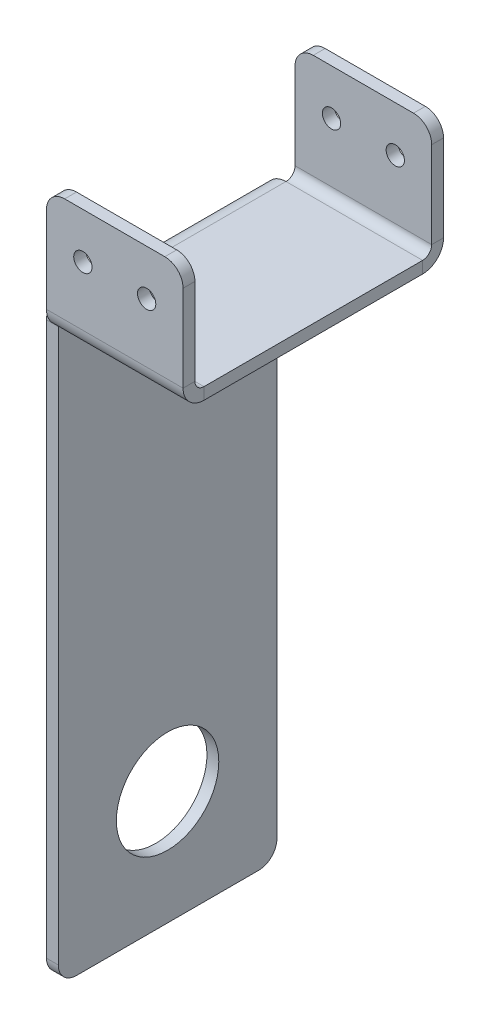
SolidWorks part; units mm, degrees
note: The reader was unsure of these and kept them because the rebuilt part matched: thickness of "Base-Flange1", "Edge-Flange1", "Edge-Flange2", "Sheet-Metal1", "Sheet-Metal2", "Sheet-Metal3", "Sheet-Metal4", "Sheet-Metal5", "Sheet-Metal6"; flange length of "Edge-Flange1", "Edge-Flange2".
ref_plane "Front Plane" through (0, 0, 0) normal (0, 0, 1) x (1, 0, 0)
ref_plane "Top Plane" through (0, 0, 0) normal (0, 1, 0) x (1, 0, 0)
ref_plane "Right Plane" through (0, 0, 0) normal (1, 0, 0) x (0, 0, -1)
sketch "Sketch1" plane through (0, 0, 0) normal (0, 1, 0) x (1, 0, 0)
  line L1 (-19.05, -30.48) -> (19.05, -30.48)
  line L2 (-19.05, -30.48) -> (-19.05, 30.48)
  line L3 (-19.05, 30.48) -> (19.05, 30.48)
  line L4 (19.05, -30.48) -> (19.05, 30.48)
  line L5 (-19.05, -30.48) -> (19.05, 30.48) construction
  line L6 (-19.05, 30.48) -> (19.05, -30.48) construction
  point P1 (0, 0)
  dimension "D1" = 38.1
  dimension "D2" = 60.96
base flange "Base-Flange1" sketch "Sketch1" thickness 3.302 reverse thickness direction no parameters "D1"=2.54
edge flange "Edge-Flange1" sketch "Sketch10" flange profiles "Sketch10", "Sketch11" flange angle 90 flange length 35.052 flange position bend outside bend radius 2.54 thickness 3.302 relief rectangular parameters "D6"=10, "D8"=0.254
sketch "Sketch10" plane through (0, 0, 30.48) normal (0, 0, 1) x (1, 0, 0)
  line L0 (-19.05, 0) -> (19.05, 0) construction
  line L1 (-19.05, 0) -> (19.05, 0)
  line L2 (-19.05, 0) -> (-19.05, 31.75)
  line L3 (-19.05, 31.75) -> (19.05, 31.75)
  line L4 (19.05, 31.75) -> (19.05, 0)
sketch "Sketch11" plane through (0, 0, -30.48) normal (0, 0, -1) x (-1, 0, 0)
  line L0 (-19.05, 0) -> (19.05, 0) construction
  line L1 (-19.05, 0) -> (19.05, 0)
  line L2 (-19.05, 0) -> (-19.05, 31.75)
  line L3 (-19.05, 31.75) -> (19.05, 31.75)
  line L4 (19.05, 31.75) -> (19.05, 0)
bend "EdgeBend1" bend radius 2.54 bend angle 90 parameters "D5"=1
bend "EdgeBend2" bend radius 2.54 bend angle 90 parameters "D5"=2
edge flange "Edge-Flange2" sketch "Sketch16" flange angle 90 flange length 165.1 flange position bend outside bend radius 2.54 thickness 3.302 parameters "D6"=10
sketch "Sketch16" plane through (-19.05, -3.302, 0) normal (-1, 0, 0) x (0, 0, -1)
  line L0 (30.48, 0) -> (-30.48, 0) construction
  line L1 (30.48, 0) -> (-30.48, 0)
  line L2 (-30.48, 0) -> (-30.48, 161.798)
  line L3 (-30.48, 161.798) -> (30.48, 161.798)
  line L4 (30.48, 161.798) -> (30.48, 0)
bend "EdgeBend3" bend radius 2.54 bend angle 90 parameters "D5"=3
sketch "Sketch17" plane through (-24.892, 0, 0) normal (-1, 0, 0) x (0, 0, 1)
  line L0 (-30.48, -165.1) -> (30.48, -165.1) construction
  circle A0 centre (0, -133.2738) radius 14.2812
  dimension "D1" = 28.5623
  dimension "D2" = 31.8262
extrude "Cut-Extrude1" cut sketch "Sketch17" against normal through all contours A0 normal cut yes
sketch "Sketch18" plane through (0, 0, 36.322) normal (0, 0, 1) x (1, 0, 0)
  line L0 (19.05, 31.75) -> (-19.05, 31.75) construction
  line L1 (19.05, 2.54) -> (19.05, 31.75) construction
  line L2 (-19.05, 31.75) -> (-19.05, 2.54) construction
  circle A0 centre (8.89, 19.05) radius 2.5527
  circle A1 centre (-8.89, 19.05) radius 2.5527
  dimension "D1" = 5.1054
  dimension "D2" = 5.1054
  dimension "D3" = 12.7
  dimension "D4" = 12.7
  dimension "D5" = 10.16
  dimension "D6" = 10.16
extrude "Cut-Extrude2" [suppressed] cut sketch "Sketch18" against normal through all
hole_wizard "1/4-20 Tapped Hole1" positions "Sketch19" profile "Sketch20" tap size "1/4-20" standard "ANSI Inch" end condition through all
sketch "Sketch19" plane through (0, 0, 36.322) normal (0, 0, 1) x (1, 0, 0)
  line L0 (19.05, 31.75) -> (-19.05, 31.75) construction
  line L1 (-19.05, 31.75) -> (-19.05, 2.54) construction
  line L2 (19.05, 2.54) -> (19.05, 31.75) construction
  point P0 (8.89, 19.05)
  point P2 (-8.89, 19.05)
  dimension "D1" = 12.7
  dimension "D2" = 12.7
  dimension "D3" = 10.16
  dimension "D4" = 10.16
sketch "Sketch20" plane through (8.89, 19.05, 36.322) normal (1, 0, 0) x (0, -1, 0)
  line L0 (0, 0) -> (0, 72.644)
  line L1 (0, 72.644) -> (2.5527, 72.644)
  line L2 (2.5527, 72.644) -> (2.5527, 0)
  line L5 (2.5527, 0) -> (0, 0)
  line L11 (0, -6.35) -> (0, 107.95) construction
  dimension "Thru Tap Drill Dia." = 5.1054
  dimension "Thru Tap Drill Depth" = 72.644
cosmetic thread "Hole Thread1"
cosmetic thread "Hole Thread2"
fillet "Fillet1" radius 5.08 6 edges at (-19.05, 31.75, 34.671) (19.05, 31.75, 34.671) (-19.05, 31.75, -34.671) (19.05, 31.75, -34.671) (-23.241, -165.1, -30.48) (-23.241, -165.1, 30.48)
sketch "Bend-Lines1" [suppressed] plane through (0, 0, 0) normal (0, 1, 0) x (1, 0, 0)
sketch "Bounding-Box1" [suppressed] plane through (0, 0, 0) normal (0, 1, 0) x (1, 0, 0)
sheet metal parameters "Sheet-Metal1" thickness 3.302 parameters "D1"=2.54, "D7"=1.6129
flat pattern "Flat-Pattern1" [suppressed]
sketch "Bend-Lines2" plane through (0, 0, 0) normal (0, 1, 0) x (1, 0, 0)
sketch3d "Bounding-Box2" [suppressed]
  line L0 (-38.1, 25.4, 0) -> (38.1, 25.4, 0) construction
  line L1 (-38.1, -25.4, 0) -> (38.1, -25.4, 0) construction
  line L2 (-38.1, 25.4, 0) -> (-38.1, -25.4, 0) construction
  line L3 (38.1, 25.4, 0) -> (38.1, -25.4, 0) construction
sheet metal parameters "Sheet-Metal2" thickness 3.302 parameters "D1"=2.54, "D7"=1.6129
flat pattern "Flat-Pattern1"
sketch "Bend-Lines2" plane through (0, 0, 0) normal (0, 1, 0) x (1, 0, 0)
  line L0 (19.05, 27.94) -> (-19.05, 27.94) construction
  line L1 (-19.05, -27.94) -> (19.05, -27.94) construction
  line L2 (19.05, 27.94) -> (-19.05, 27.94) construction
  line L3 (-19.05, -27.94) -> (19.05, -27.94) construction
sketch3d "Bounding-Box2" [suppressed]
  line L0 (-19.05, -61.3791, 0) -> (-19.05, 61.3791, 0) construction
  line L1 (19.05, -61.3791, 0) -> (19.05, 61.3791, 0) construction
  line L2 (-19.05, -61.3791, 0) -> (19.05, -61.3791, 0) construction
  line L3 (-19.05, 61.3791, 0) -> (19.05, 61.3791, 0) construction
bend of the flat pattern "Flatten-<EdgeBend1>1"
bend of the flat pattern "Flatten-<EdgeBend2>1"
sheet metal parameters "Sheet-Metal3" thickness 3.302 parameters "D1"=2.54, "D7"=1.6129
flat pattern "Flat-Pattern1"
sketch "Bend-Lines2" plane through (0, 0, 0) normal (0, 1, 0) x (1, 0, 0)
  line L0 (19.05, 27.94) -> (-19.05, 27.94) construction
  line L1 (-19.05, -27.94) -> (19.05, -27.94) construction
  line L2 (19.05, 27.94) -> (-19.05, 27.94) construction
  line L3 (-19.05, -27.94) -> (19.05, -27.94) construction
  line L4 (-21.59, 25.4) -> (-21.59, -25.4) construction
  line L5 (-21.59, 25.4) -> (-21.59, -25.4) construction
sketch3d "Bounding-Box2" [suppressed]
  line L0 (19.05, 61.3791, 0) -> (-134.2771, 61.3791, 0) construction
  line L1 (19.05, -61.3791, 0) -> (-134.2771, -61.3791, 0) construction
  line L2 (19.05, 61.3791, 0) -> (19.05, -61.3791, 0) construction
  line L3 (-134.2771, 61.3791, 0) -> (-134.2771, -61.3791, 0) construction
bend of the flat pattern "Flatten-<EdgeBend1>1"
bend of the flat pattern "Flatten-<EdgeBend2>1"
bend of the flat pattern "Flatten-<EdgeBend3>1"
sheet metal parameters "Sheet-Metal4" thickness 3.302 parameters "D1"=2.54, "D7"=1.6129
flat pattern "Flat-Pattern1"
sketch "Bend-Lines2" plane through (0, 0, 0) normal (0, 1, 0) x (1, 0, 0)
  line L0 (19.05, 33.02) -> (-19.05, 33.02) construction
  line L1 (-19.05, -33.02) -> (19.05, -33.02) construction
  line L2 (19.05, 33.02) -> (-19.05, 33.02) construction
  line L3 (-19.05, -33.02) -> (19.05, -33.02) construction
  line L4 (-21.59, 30.48) -> (-21.59, -30.48) construction
  line L5 (-21.59, 30.48) -> (-21.59, -30.48) construction
sketch3d "Bounding-Box2" [suppressed]
  line L0 (19.05, 64.77, 0) -> (-183.388, 64.77, 0) construction
  line L1 (19.05, -64.77, 0) -> (-183.388, -64.77, 0) construction
  line L2 (19.05, 64.77, 0) -> (19.05, -64.77, 0) construction
  line L3 (-183.388, 64.77, 0) -> (-183.388, -64.77, 0) construction
bend of the flat pattern "Flatten-<EdgeBend1>1"
bend of the flat pattern "Flatten-<EdgeBend2>1"
bend of the flat pattern "Flatten-<EdgeBend3>1"
sheet metal parameters "Sheet-Metal5" thickness 3.302 parameters "D1"=2.54, "D7"=1.6129
flat pattern "Flat-Pattern1"
sketch "Bend-Lines2" plane through (0, 0, 0) normal (0, 1, 0) x (1, 0, 0)
  line L0 (19.05, 33.02) -> (-19.05, 33.02) construction
  line L1 (-19.05, -33.02) -> (19.05, -33.02) construction
  line L2 (19.05, 33.02) -> (-19.05, 33.02) construction
  line L3 (-19.05, -33.02) -> (19.05, -33.02) construction
  line L4 (-21.59, 30.48) -> (-21.59, -30.48) construction
  line L5 (-21.59, 30.48) -> (-21.59, -30.48) construction
sketch3d "Bounding-Box2" [suppressed]
  line L0 (19.05, 64.77, 0) -> (-183.388, 64.77, 0) construction
  line L1 (19.05, -64.77, 0) -> (-183.388, -64.77, 0) construction
  line L2 (19.05, 64.77, 0) -> (19.05, -64.77, 0) construction
  line L3 (-183.388, 64.77, 0) -> (-183.388, -64.77, 0) construction
bend of the flat pattern "Flatten-<EdgeBend1>1"
bend of the flat pattern "Flatten-<EdgeBend2>1"
bend of the flat pattern "Flatten-<EdgeBend3>1"
sheet metal parameters "Sheet-Metal6" thickness 3.302 parameters "D1"=2.54, "D7"=1.6129
flat pattern "Flat-Pattern1"
sketch "Bend-Lines2" plane through (0, 0, 0) normal (0, 1, 0) x (1, 0, 0)
  line L0 (19.05, 33.02) -> (-19.05, 33.02) construction
  line L1 (-19.05, -33.02) -> (19.05, -33.02) construction
  line L2 (19.05, 33.02) -> (-19.05, 33.02) construction
  line L3 (-19.05, -33.02) -> (19.05, -33.02) construction
  line L4 (-21.59, 30.48) -> (-21.59, -30.48) construction
  line L5 (-21.59, 30.48) -> (-21.59, -30.48) construction
sketch3d "Bounding-Box2" [suppressed]
  line L0 (-183.388, 64.7699, 0) -> (19.05, 64.77, 0) construction
  line L1 (-183.388, -64.7701, 0) -> (19.0501, -64.77, 0) construction
  line L2 (-183.388, 64.7699, 0) -> (-183.388, -64.7701, 0) construction
  line L3 (19.05, 64.77, 0) -> (19.0501, -64.77, 0) construction
bend of the flat pattern "Flatten-<EdgeBend1>1"
bend of the flat pattern "Flatten-<EdgeBend2>1"
bend of the flat pattern "Flatten-<EdgeBend3>1"
equation "\"D2@Sketch18\"=\"D1@Sketch18\""
